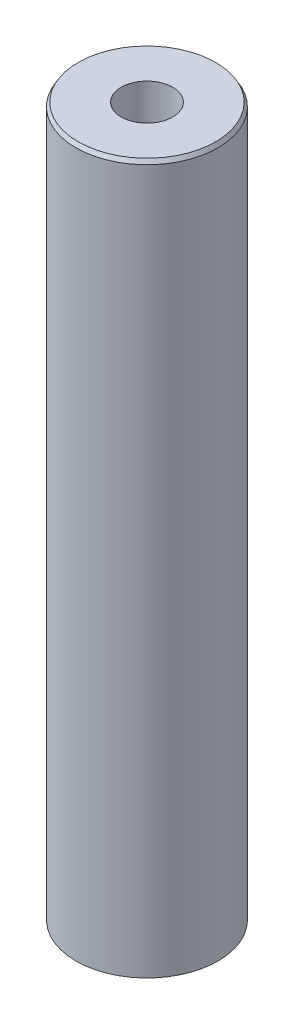
SolidWorks part; units mm, degrees
ref_plane "Front Plane" through (0, 0, 0) normal (0, 0, 1) x (1, 0, 0)
ref_plane "Top Plane" through (0, 0, 0) normal (0, 1, 0) x (1, 0, 0)
ref_plane "Right Plane" through (0, 0, 0) normal (1, 0, 0) x (0, 0, -1)
sketch "Sketch1" plane through (0, 0, 0) normal (0, 1, 0) x (1, 0, 0)
  circle A0 centre (0, 0) radius 60
  dimension "SHAFT_OD" = 120
extrude "Boss-Extrude1" add sketch "Sketch1" along normal blind 600
sketch "Sketch2" plane through (0, 0, 0) normal (0, 1, 0) x (1, 0, 0)
  circle A0 centre (0, 0) radius 21.7583
  dimension "BORE_D" = 43.5165
extrude "Cut-Extrude1" cut sketch "Sketch2" along normal through all
chamfer "Chamfer1" distance 3.3874 angle 30 2 edges at (0, 600, 60) (0, 0, 60) first distance on face at (0, 600, 60) first distance on face at (0, 0, 21.7583)
